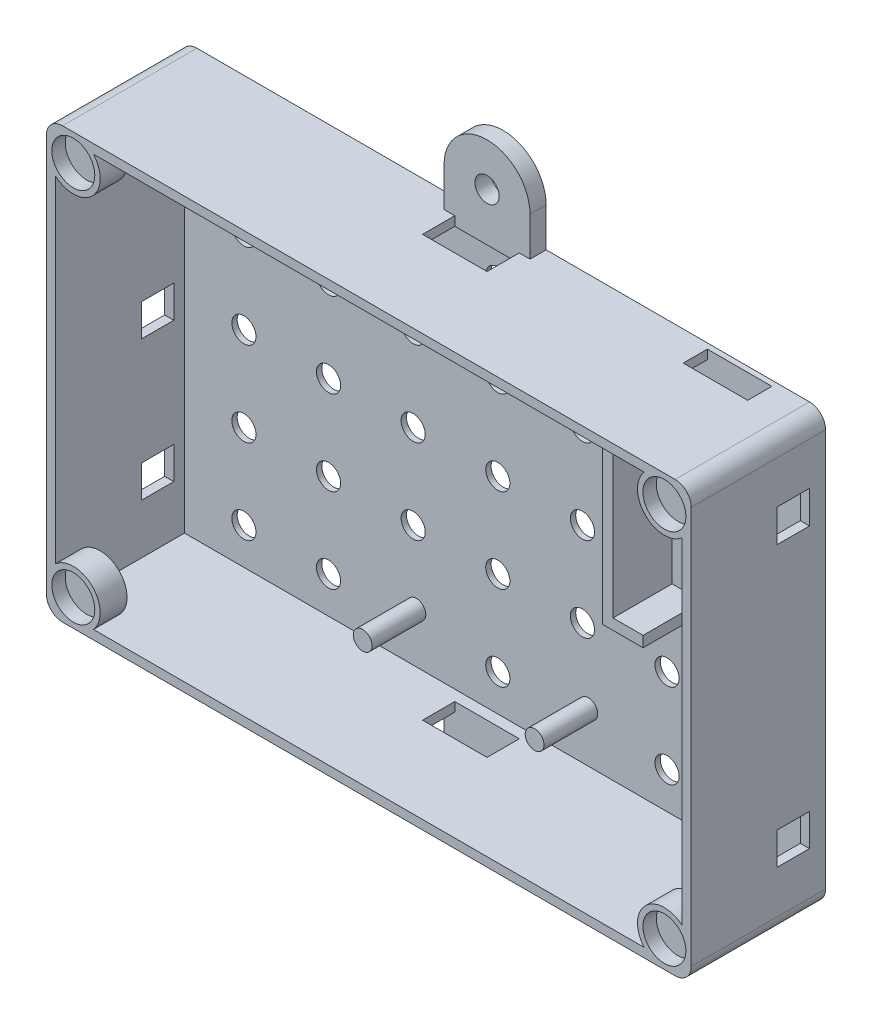
SolidWorks part; units mm, degrees
ref_plane "Front Plane" through (0, 0, 0) normal (0, 0, 1) x (1, 0, 0)
ref_plane "Top Plane" through (0, 0, 0) normal (0, 1, 0) x (1, 0, 0)
ref_plane "Right Plane" through (0, 0, 0) normal (1, 0, 0) x (0, 0, -1)
sketch "Sketch1" plane through (0, 0, 0) normal (0, 0, 1) x (1, 0, 0)
  line L1 (0, 0) -> (120, 0)
  line L2 (0, 0) -> (0, 80)
  line L3 (0, 80) -> (120, 80)
  line L4 (120, 0) -> (120, 80)
  dimension "D1" = 120
  dimension "D2" = 80
extrude "Boss-Extrude1" add sketch "Sketch1" along normal blind 25
sketch "Sketch2" plane through (0, 0, 25) normal (0, 0, 1) x (1, 0, 0)
  line L1 (1.7, 78.3) -> (118.3, 78.3)
  line L2 (1.7, 78.3) -> (1.7, 1.7)
  line L3 (1.7, 1.7) -> (118.3, 1.7)
  line L4 (118.3, 78.3) -> (118.3, 1.7)
  line L5 (120, 80) -> (0, 80) construction
  line L6 (120, 0) -> (120, 80) construction
  line L8 (0, 80) -> (0, 0) construction
  line L9 (0, 0) -> (120, 0) construction
  dimension "D1" = 1.7
  dimension "D2" = 1.7
  dimension "D3" = 1.7
  dimension "D4" = 1.7
extrude "Cut-Extrude1" cut sketch "Sketch2" against normal blind 24
ref_plane "Plane3" through (0, 40, 0) normal (0, 1, 0) x (1, 0, 0)
sketch "Sketch4" plane through (0, 0, 0) normal (0, 0, -1) x (-1, 0, 0)
  line L0 (-60.5845, 89.8239) -> (-60.5845, -8.7853) construction
  line L1 (-68, 80) -> (-68, 87.25)
  line L2 (-120, 80) -> (0, 80) construction
  line L3 (-52, 87.25) -> (-52, 80)
  line L6 (-68, 0) -> (-68, -7.25)
  line L7 (0, 0) -> (-120, 0) construction
  line L9 (-52, -7.25) -> (-52, 0)
  line L10 (-68, 80) -> (-52, 80)
  line L11 (-68, 0) -> (-52, 0)
  line L16 (-120, 0) -> (-120, 80) construction
  line L17 (13.75, 40) -> (-13.75, 40) construction
  arc A0 (-68, 87.25) -> (-52, 87.25) centre (-60, 87.25) cw
  arc A1 (-68, -7.25) -> (-52, -7.25) centre (-60, -7.25) ccw
  circle A2 centre (-60, 87.25) radius 2.25
  circle A3 centre (-60, -7.25) radius 2.25
  dimension "D2" = 8
  dimension "D4" = 4.5
  dimension "D1" = 94.5
  dimension "D3" = 60
extrude "Boss-Extrude3" add sketch "Sketch4" against normal blind 3
sketch "Sketch6" plane through (0, 0, 0) normal (0, 0, 1) x (1, 0, 0)
  line L0 (90.44, 78.3) -> (92.44, 78.3)
  line L1 (90.44, 78.3) -> (90.44, 36.89)
  line L2 (90.44, 36.89) -> (98.04, 36.89)
  line L3 (92.44, 78.3) -> (92.44, 38.89)
  line L5 (98.04, 36.89) -> (98.04, 38.89)
  line L6 (98.04, 38.89) -> (92.44, 38.89)
  line L7 (118.3, 38.89) -> (113.24, 38.89)
  line L8 (113.24, 36.89) -> (118.3, 36.89)
  line L9 (113.24, 36.89) -> (113.24, 38.89)
  line L10 (118.3, 36.89) -> (118.3, 38.89)
  line L20 (118.3, 1.7) -> (118.3, 78.3) construction
  line L21 (118.3, 78.3) -> (1.7, 78.3) construction
  point P1 (98.04, 37.89)
  dimension "D1" = 2
  dimension "D2" = 2
  dimension "D3" = 41.41
  dimension "D4" = 7.6
  dimension "D5" = 15.2
  dimension "D6" = 5.06
extrude "Boss-Extrude4" add sketch "Sketch6" along normal blind 12
sketch "Sketch7" plane through (0, 0, 1) normal (0, 0, 1) x (1, 0, 0)
  line L0 (120, 0) -> (120, 80) construction
  line L3 (1.7, 1.7) -> (118.3, 1.7) construction
  circle A0 centre (44.85, 69) radius 1.75
  circle A1 centre (44.85, 11) radius 1.75
  circle A2 centre (76.85, 69) radius 1.75
  circle A3 centre (76.85, 11) radius 1.75
  dimension "D1" = 58
  dimension "D2" = 32
  dimension "D3" = 58
  dimension "D4" = 9.3
  dimension "D5" = 43.15
extrude "Boss-Extrude5" add sketch "Sketch7" along normal blind 10
sketch "Sketch8" plane through (0, 0, 25) normal (0, 0, 1) x (1, 0, 0)
  line L0 (120, 80) -> (0, 80) construction
  line L1 (0, 80) -> (0, 0) construction
  circle A0 centre (5, 75) radius 5
  dimension "D1" = 10
extrude "Boss-Extrude6" add sketch "Sketch8" against normal blind 5
sketch "Sketch9" plane through (0, 0, 25) normal (0, 0, 1) x (1, 0, 0)
  line L0 (120, 80) -> (0, 80) construction
  line L1 (0, 80) -> (0, 0) construction
  circle A0 centre (5, 75) radius 4
  arc A1 (1.7, 71.2437) -> (8.7563, 78.3) centre (5, 75) ccw construction
  dimension "D1" = 5
  dimension "D3" = 8
  dimension "D2" = 5
extrude "Cut-Extrude2" cut sketch "Sketch9" against normal blind 2.5
ref_plane "Plane4" through (60, 0, 0) normal (-1, 0, 0) x (0, 0, 1)
mirror "Mirror1" about plane through (60, 0, 0) normal (-1, 0, 0) of "Boss-Extrude6", "Cut-Extrude2"
ref_plane "Plane5" through (0, 40, 0) normal (0, 1, 0) x (1, 0, 0)
mirror "Mirror2" about plane through (0, 40, 0) normal (0, 1, 0) of "Mirror1", "Cut-Extrude2", "Boss-Extrude6"
fillet "Fillet1" radius 3 4 edges at (120, 0, 12.5) (120, 80, 12.5) (0, 80, 12.5) (0, 0, 12.5)
sketch "Sketch10" plane through (0, 0, 0) normal (0, 0, -1) x (-1, 0, 0)
  line L0 (-60, 95.25) -> (-60, -15.25) construction
  circle A0 centre (-107.25, 8.5) radius 2.25
  circle A1 centre (-60, -7.25) radius 2.25 construction
  circle A2 centre (-91.5, 8.5) radius 2.25
  circle A4 centre (-60, 8.5) radius 2.25
  arc A5 (-52, 87.25) -> (-68, 87.25) centre (-60, 87.25) ccw construction
  arc A6 (-68, -7.25) -> (-52, -7.25) centre (-60, -7.25) ccw construction
  circle A7 centre (-91.5, 8.5) radius 2.25
  circle A9 centre (-60, 8.5) radius 2.25
  circle A12 centre (-60, 8.5) radius 2.25
  circle A14 centre (-28.5, 8.5) radius 2.25
  circle A15 centre (-60, 8.5) radius 2.25
  circle A17 centre (-28.5, 8.5) radius 2.25
  circle A18 centre (-12.75, 8.5) radius 2.25
  circle A19 centre (-91.5, 24.25) radius 2.25
  circle A20 centre (-75.75, 24.25) radius 2.25
  circle A21 centre (-60, 24.25) radius 2.25
  circle A22 centre (-44.25, 24.25) radius 2.25
  circle A23 centre (-75.75, 24.25) radius 2.25
  circle A24 centre (-60, 24.25) radius 2.25
  circle A25 centre (-44.25, 24.25) radius 2.25
  circle A26 centre (-28.5, 24.25) radius 2.25
  circle A27 centre (-60, 24.25) radius 2.25
  circle A28 centre (-44.25, 24.25) radius 2.25
  circle A29 centre (-28.5, 24.25) radius 2.25
  circle A30 centre (-12.75, 24.25) radius 2.25
  circle A32 centre (-75.75, 40) radius 2.25
  circle A33 centre (-60, 40) radius 2.25
  circle A34 centre (-44.25, 40) radius 2.25
  circle A35 centre (-75.75, 40) radius 2.25
  circle A36 centre (-60, 40) radius 2.25
  circle A37 centre (-44.25, 40) radius 2.25
  circle A38 centre (-28.5, 40) radius 2.25
  circle A39 centre (-60, 40) radius 2.25
  circle A40 centre (-44.25, 40) radius 2.25
  circle A41 centre (-28.5, 40) radius 2.25
  circle A42 centre (-12.75, 40) radius 2.25
  circle A44 centre (-75.75, 55.75) radius 2.25
  circle A45 centre (-60, 55.75) radius 2.25
  circle A46 centre (-44.25, 55.75) radius 2.25
  circle A47 centre (-75.75, 55.75) radius 2.25
  circle A48 centre (-60, 55.75) radius 2.25
  circle A49 centre (-44.25, 55.75) radius 2.25
  circle A50 centre (-28.5, 55.75) radius 2.25
  circle A51 centre (-60, 55.75) radius 2.25
  circle A52 centre (-44.25, 55.75) radius 2.25
  circle A53 centre (-28.5, 55.75) radius 2.25
  circle A54 centre (-12.75, 55.75) radius 2.25
  circle A57 centre (-60, 71.5) radius 2.25
  circle A60 centre (-60, 71.5) radius 2.25
  circle A62 centre (-28.5, 71.5) radius 2.25
  circle A63 centre (-60, 71.5) radius 2.25
  circle A65 centre (-28.5, 71.5) radius 2.25
  circle A66 centre (-12.75, 71.5) radius 2.25
  circle A67 centre (-107.25, 24.25) radius 2.25
  circle A68 centre (-91.5, 24.25) radius 2.25
  circle A69 centre (-75.75, 24.25) radius 2.25
  circle A70 centre (-60, 24.25) radius 2.25
  circle A71 centre (-107.25, 40) radius 2.25
  circle A73 centre (-75.75, 40) radius 2.25
  circle A74 centre (-60, 40) radius 2.25
  circle A75 centre (-107.25, 55.75) radius 2.25
  circle A77 centre (-75.75, 55.75) radius 2.25
  circle A78 centre (-60, 55.75) radius 2.25
  circle A79 centre (-107.25, 71.5) radius 2.25
  circle A82 centre (-60, 71.5) radius 2.25
  circle A83 centre (-44.25, 8.5) radius 2.25 [skipped]
  circle A85 centre (-44.25, 8.5) radius 2.25 [skipped]
  circle A86 centre (-75.75, 8.5) radius 2.25 [skipped]
  circle A87 centre (-75.75, 8.5) radius 2.25 [skipped]
  circle A88 centre (-75.75, 8.5) radius 2.25 [skipped]
  circle A89 centre (-44.25, 71.5) radius 2.25 [skipped]
  circle A90 centre (-44.25, 71.5) radius 2.25 [skipped]
  circle A91 centre (-75.75, 71.5) radius 2.25 [skipped]
  circle A92 centre (-75.75, 71.5) radius 2.25 [skipped]
  circle A93 centre (-91.5, 71.5) radius 2.25 [skipped]
  circle A94 centre (-91.5, 55.75) radius 2.25 [skipped]
  circle A95 centre (-91.5, 40) radius 2.25 [skipped]
  circle A96 centre (-91.5, 40) radius 2.25 [skipped]
  circle A97 centre (-91.5, 55.75) radius 2.25 [skipped]
  circle A98 centre (-91.5, 71.5) radius 2.25 [skipped]
  dimension "D1" = 15.75
  dimension "D2" = 4
  dimension "D3" = 4
  dimension "D4" = 5
extrude "Cut-Extrude3" cut sketch "Sketch10" against normal blind 2 contours A62 | A54 | A50 | A42 | A38 | A34 | A30 | A26 | A22 | A18 | L0 A21 | A15 L0 | A70 L0 | A74 L0 | L0 A33 | A78 L0 | L0 A45 | L0 A57 | A82 L0 | A20 | A44 | A32 | A19 | A67 | A0 | A75 | A71 | A66 | A46 | A14 | A4 | A2 | A79 region at (59.0451, 71.5, 0) region at (59.0451, 8.5, 0) region at (59.0451, 24.25, 0) region at (60.9549, 24.25, 0) region at (59.0451, 40, 0) region at (60.9549, 40, 0) region at (59.0451, 55.75, 0) region at (60.9549, 55.75, 0) region at (60.9549, 71.5, 0) region at (107.25, 8.5, 0) region at (12.75, 8.5, 0) region at (91.5, 24.25, 0) region at (75.75, 24.25, 0) region at (44.25, 24.25, 0) region at (28.5, 24.25, 0) region at (12.75, 24.25, 0) region at (75.75, 40, 0) region at (44.25, 40, 0) region at (28.5, 40, 0) region at (12.75, 40, 0) region at (75.75, 55.75, 0) region at (28.5, 55.75, 0) region at (12.75, 55.75, 0) region at (28.5, 71.5, 0) region at (107.25, 24.25, 0) region at (107.25, 40, 0) region at (107.25, 55.75, 0)
sketch "Sketch11" plane through (0, 80, 0) normal (0, 1, 0) x (1, 0, 0)
  line L0 (26.25, -1) -> (30.75, -1) construction
  line L1 (99, -5.5) -> (111, -5.5)
  line L2 (99, -5.5) -> (99, -1)
  line L3 (99, -1) -> (111, -1)
  line L4 (111, -5.5) -> (111, -1)
  line L6 (117, -25) -> (117, 0) construction
  dimension "D1" = 12
  dimension "D2" = 4.5
  dimension "D3" = 6
extrude "Cut-Extrude4" cut sketch "Sketch11" against normal up to next
sketch "Sketch12" plane through (0, 0, 0) normal (0, -1, 0) x (1, 0, 0)
  line L0 (52, 3) -> (68, 3) construction
  line L1 (60, 3) -> (54, 3)
  line L3 (60, 9) -> (54, 9)
  line L4 (54, 3) -> (54, 9)
  line L5 (60, 9) -> (66, 9)
  line L6 (66, 9) -> (66, 3)
  line L7 (68, 3) -> (52, 3) construction
  line L8 (66, 3) -> (60, 3)
  dimension "D1" = 6
  dimension "D2" = 6
  dimension "D3" = 6
extrude "Cut-Extrude5" cut sketch "Sketch12" against normal through all both and the other way through all
sketch "Sketch13" plane through (0, 0, 0) normal (-1, 0, 0) x (0, 0, 1)
  line L0 (3, 80) -> (3, 87.25) construction
  line L2 (3, 40) -> (3, 43)
  line L3 (3, 43) -> (9, 43)
  line L4 (9, 40) -> (9, 43)
  line L5 (0, 40) -> (3, 40) construction
  line L6 (0, 77) -> (0, 3) construction
  line L7 (25, 77) -> (25, 3) construction
  line L8 (3, 40) -> (3, 37)
  line L9 (3, 37) -> (9, 37)
  line L10 (9, 37) -> (9, 40)
  line L11 (9, 40) -> (25, 40) construction
  line L12 (3, 65) -> (3, 69.0701)
  line L13 (3, 69.0701) -> (9, 69.0701)
  line L14 (9, 66) -> (9, 69.0701)
  line L15 (3, 65) -> (3, 63)
  line L16 (3, 63) -> (9, 63)
  line L17 (9, 63) -> (9, 66)
  line L18 (3, 17) -> (3, 11)
  line L19 (3, 11) -> (9, 11)
  line L20 (9, 15.0868) -> (9, 11)
  line L22 (3, 17) -> (9, 17)
  line L23 (9, 17) -> (9, 15.0868)
  line L24 (3, -7.25) -> (3, 0) construction
  dimension "D1" = 6
  dimension "D2" = 3
  dimension "D3" = 3
  dimension "D4" = 20
  dimension "D5" = 20
  dimension "D6" = 6
  dimension "D7" = 6
extrude "Cut-Extrude6" cut sketch "Sketch13" against normal up to surface (1.7 mm away) and the other way through all up to face at (1.7, 40, 16.5)
ref_plane "Plane6" through (60, 0, 0) normal (-1, 0, 0) x (0, 0, 1)
mirror "Mirror3" about plane through (60, 0, 0) normal (-1, 0, 0) of face at (0.85, 17, 6) of face at (0.85, 14, 3) of face at (0.85, 14, 9) of face at (0.85, 11, 6) of face at (0.85, 63, 6) of face at (0.85, 66.0351, 9) of face at (0.85, 69.0701, 6) of face at (0.85, 66.0351, 3)
